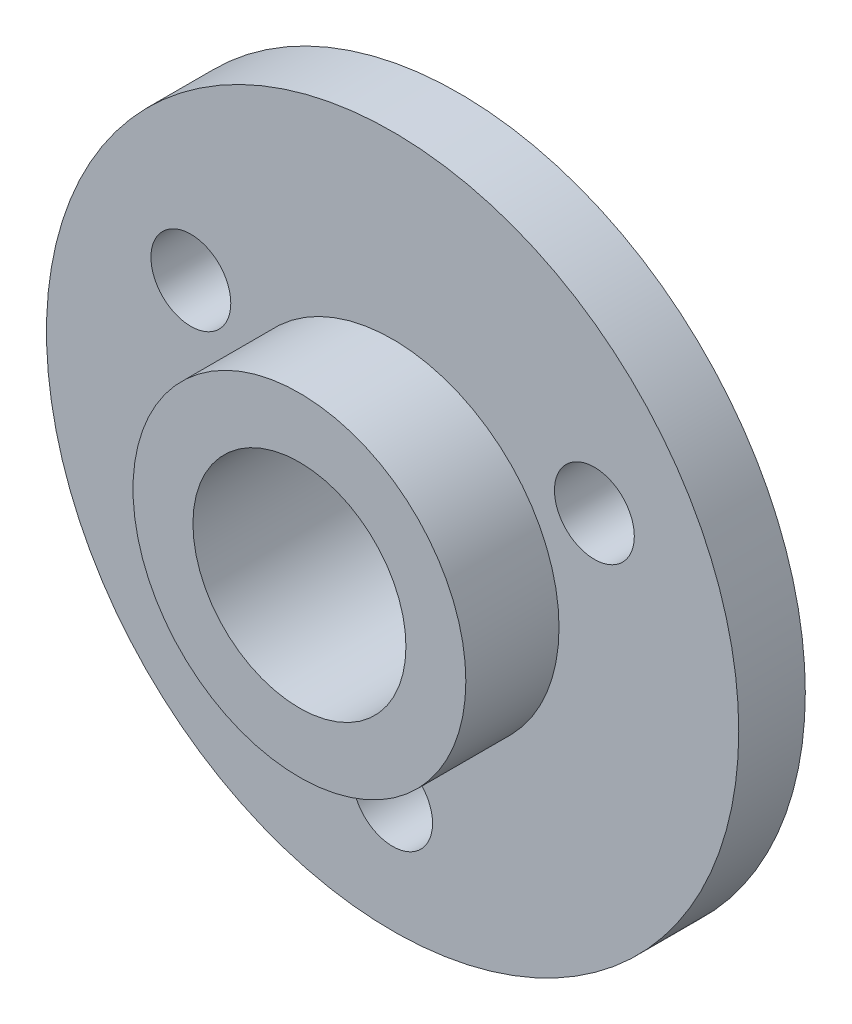
SolidWorks part; units mm, degrees
material "AISI 304"
ref_plane "Plano frontal" through (0, 0, 0) normal (0, 0, 1) x (1, 0, 0)
ref_plane "Plano superior" through (0, 0, 0) normal (0, 1, 0) x (1, 0, 0)
ref_plane "Plano direito" through (0, 0, 0) normal (1, 0, 0) x (0, 0, -1)
sketch "Esboço2" plane through (0, 0, 0) normal (0, 0, 1) x (1, 0, 0)
  line L0 (-92.3668, 0) -> (92.3668, 0) construction
  line L1 (0, 66.6434) -> (0, -66.6434) construction
  line L2 (-30.3109, 17.5) -> (0, 0) construction
  line L3 (30.3109, 17.5) -> (0, 0) construction
  circle A0 centre (0, 0) radius 26
  circle A1 centre (0, 0) radius 17.5 construction
  circle A2 centre (0, 0) radius 12.5
  circle A3 centre (0, 0) radius 8
  circle A4 centre (15.1554, 8.75) radius 3
  circle A5 centre (-15.1554, 8.75) radius 3
  circle A6 centre (0, -17.5) radius 3
  point P9 (0, 0)
  point P12 (0, 0)
  point P21 (-15.1554, 8.75)
  point P23 (15.1554, 8.75)
  dimension "D1" = 52
  dimension "D2" = 16
  dimension "D3" = 25
  dimension "D4" = 35
  dimension "D5" = 6
  dimension "D6" = 6
  dimension "D7" = 30
extrude "Ressalto-extrusão1" add sketch "Esboço2" along normal blind 5 contours A0 A6 A5 A4 A2 | A2 A3 region at (-25.2646, 0, 0) region at (-12.1464, 0, 0)
extrude "Ressalto-extrusão3" add sketch "Esboço2<4>" along normal blind 12 contours A2 A3 region at (-12.1464, 0, 0)
sketch "Esboço2<4>" plane through (0, 0, 0) normal (0, 0, 1) x (1, 0, 0) same geometry as "Esboço2"
